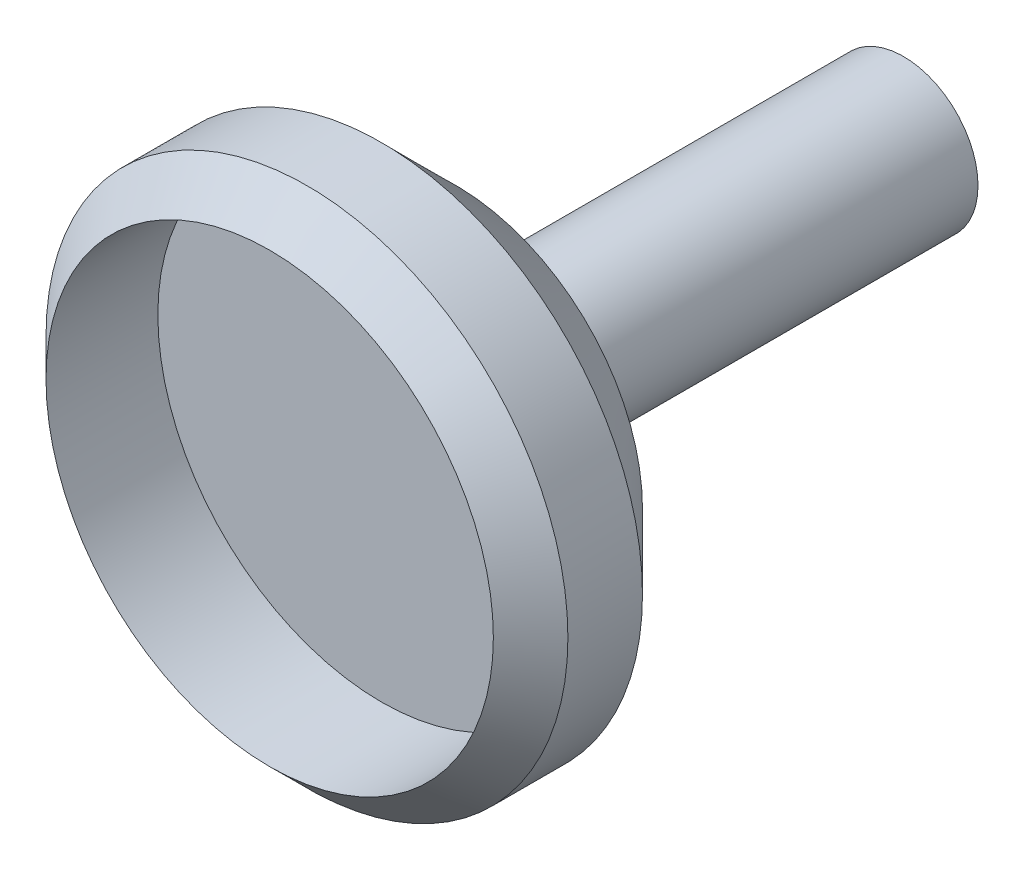
SolidWorks part; units mm, degrees
ref_plane "Plano frontal" through (0, 0, 0) normal (0, 0, 1) x (1, 0, 0)
ref_plane "Plano superior" through (0, 0, 0) normal (0, 1, 0) x (1, 0, 0)
ref_plane "Plano direito" through (0, 0, 0) normal (1, 0, 0) x (0, 0, -1)
sketch "Esboço1" plane through (0, 0, 0) normal (0, 0, 1) x (1, 0, 0)
  circle A0 centre (0, 0) radius 1
  circle A1 centre (0, 0) radius 0.5
  dimension "D1" = 2
  dimension "D2" = 1
extrude "Ressalto-extrusão1" add sketch "Esboço1" along normal blind 6
sketch "Esboço3" plane through (0, 0, 6) normal (0, 0, 1) x (1, 0, 0)
  circle A0 centre (0, 0) radius 3.5
  dimension "D1" = 7
extrude "Ressalto-extrusão2" add sketch "Esboço3" along normal blind 3 contours A0
sketch "Esboço4" plane through (0, 0, 9) normal (0, 0, 1) x (1, 0, 0)
  circle A0 centre (0, 0) radius 3
  dimension "D1" = 6
extrude "Corte-extrusão1" cut sketch "Esboço4" against normal blind 2
chamfer "Chanfro1" distance 1 angle 45 2 edges at (3.5, 0, 9) (3.5, 0, 6)
